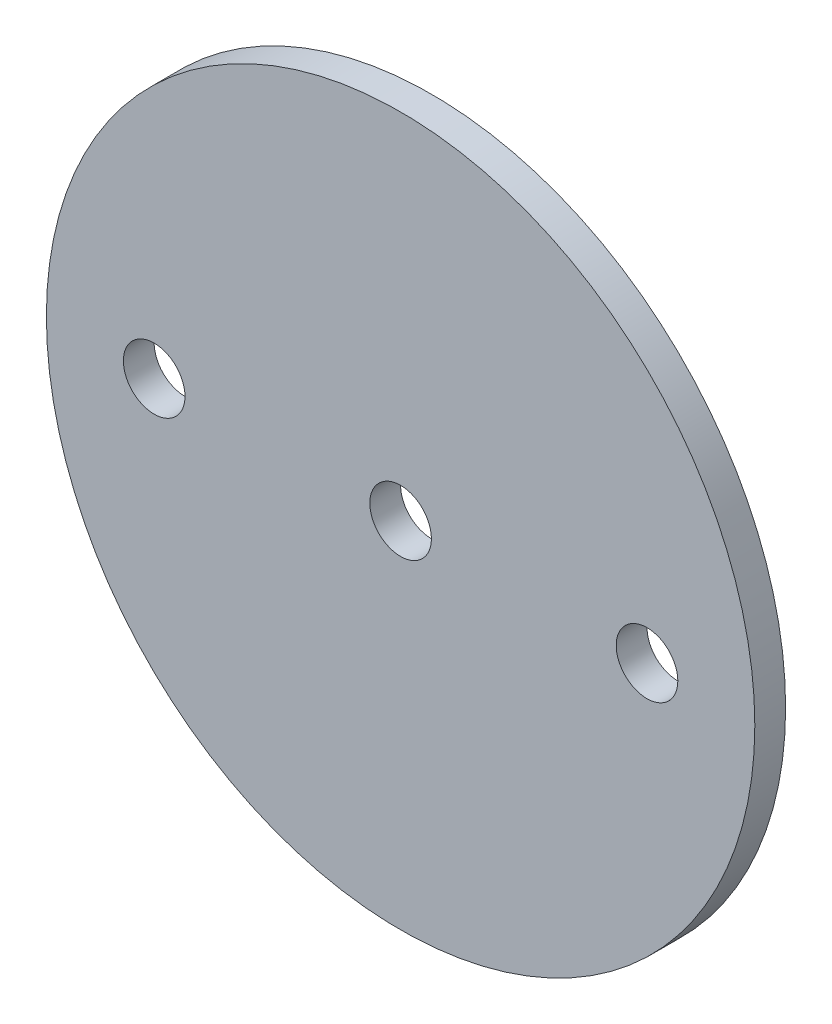
SolidWorks part; units mm, degrees
ref_plane "Front Plane" through (0, 0, 0) normal (0, 0, 1) x (1, 0, 0)
ref_plane "Top Plane" through (0, 0, 0) normal (0, 1, 0) x (1, 0, 0)
ref_plane "Right Plane" through (0, 0, 0) normal (1, 0, 0) x (0, 0, -1)
sketch "Sketch1" plane through (0, 0, 0) normal (0, 0, 1) x (1, 0, 0)
  circle A0 centre (0, 0) radius 36.5125
  dimension "D1" = 73.025
extrude "Boss-Extrude1" add sketch "Sketch1" along normal mid plane 3.175
sketch "Sketch2" plane through (0, 0, 1.5875) normal (0, 0, 1) x (1, 0, 0)
  line L0 (-1000, 0) -> (49000, 0) construction
  point P1 (0, 0)
  point P4 (25.4, 0)
  point P5 (-25.4, 0)
  dimension "D1" = 25.4
  dimension "D2" = 50.8
hole_wizard "1/4 (0.25) Diameter Hole1" positions "Sketch2" profile "Sketch3" hole size "1/4" standard "ANSI Inch" end condition through all
sketch "Sketch3" plane through (-25.4, 0, 1.5875) normal (1, 0, 0) x (0, -1, 0)
  line L0 (0, 0) -> (0, 3.175)
  line L1 (0, 3.175) -> (3.175, 3.175)
  line L2 (3.175, 3.175) -> (3.175, 0)
  line L5 (3.175, 0) -> (0, 0)
  line L11 (0, -6.35) -> (0, 107.95) construction
  dimension "Thru Hole Dia." = 6.35
  dimension "Thru Hole Depth" = 3.175
equation "\"AIRFRAME_OD\"= 3.142in"
equation "\"AIRFRAME_ID\"= 3.00in"
equation "\"FLAT_T\"= 0.125in"
equation "\"NOSE_EXP_L\"= 3.5in"
equation "\"NOSE_SHOULDER_L\"= 1.5in"
equation "\"MAIN_L\"= 30in"
equation "\"RECO_COUP_L\"= 6in"
equation "\"RECO_SWITCH_L\"= 1.5in"
equation "\"DROGUE_L\"= 14in"
equation "\"ATS_FORE_COUP_L\"= 4in"
equation "\"ATS_AFT_COUP_L\"= 2.5in"
equation "\"LOWER_L\"= 16in"
equation "\"FIN_N\"= 4"
equation "\"CR_AFT_X\"= 0.5in"
equation "\"CR_FORE_X\"= 6in"
equation "\"FIN_ROOT\"= 5in"
equation "\"FIN_X\"= 0.75in"
equation "\"MOTOR_OD\"= 2.25in"
equation "\"MOTOR_ID\"= 2.126in"
equation "\"COUPLER_OD\"= 2.998in"
equation "\"COUPLER_ID\"= 2.875in"
equation "\"D1@Sketch1\"=\"COUPLER_ID\""
equation "\"D1@Boss-Extrude1\"=\"FLAT_T\""
equation "\"RECO_ROD_X\"= 1.5in"
equation "\"ATS_ROD_X\"= 2in"
equation "\"D1@Sketch2\"=\"ATS_ROD_X\"*0.5"
equation "\"D2@Sketch2\"=\"ATS_ROD_X\""
